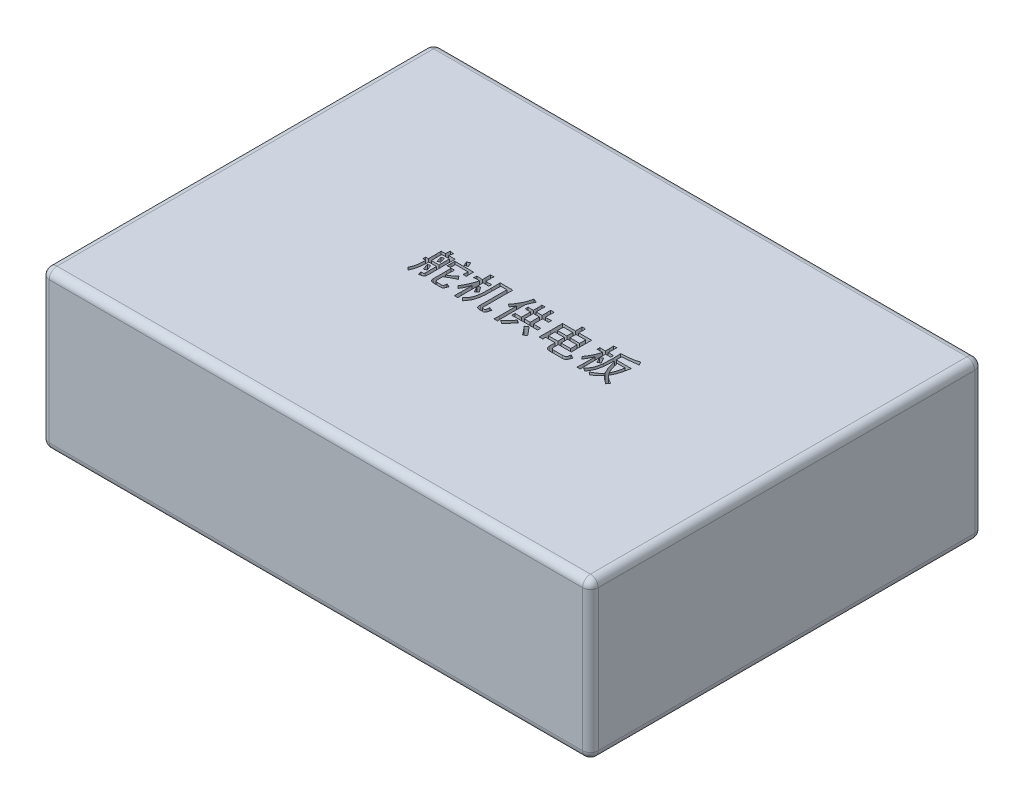
SolidWorks part; units mm, degrees
ref_plane "前视基准面" through (0, 0, 0) normal (0, 0, 1) x (1, 0, 0)
ref_plane "上视基准面" through (0, 0, 0) normal (0, 1, 0) x (1, 0, 0)
ref_plane "右视基准面" through (0, 0, 0) normal (1, 0, 0) x (0, 0, -1)
sketch "草图1" plane through (0, 0, 0) normal (0, 1, 0) x (1, 0, 0)
  line L1 (-35, 25) -> (35, 25)
  line L2 (-35, 25) -> (-35, -25)
  line L3 (-35, -25) -> (35, -25)
  line L4 (35, 25) -> (35, -25)
  line L5 (-35, 25) -> (35, -25) construction
  line L6 (-35, -25) -> (35, 25) construction
  point P0 (0, 0)
  dimension "D1" = 70
  dimension "D2" = 50
extrude "凸台-拉伸1" add sketch "草图1" along normal blind 20
sketch "草图2" plane through (0, 20, 0) normal (0, 1, 0) x (1, 0, 0)
  text T0 "舵机供电板" font "黑体" height 3.5
extrude "切除-拉伸1" cut sketch "草图2" against normal blind 2
fillet "圆角1" radius 1 12 edges at (0, 20, -25) (35, 20, 0) (35, 10, -25) (0, 20, 25) (35, 10, 25) (0, 0, -25) (0, 0, 25) (35, 0, 0) (-35, 10, -25) (-35, 20, 0) (-35, 10, 25) (-35, 0, 0)
